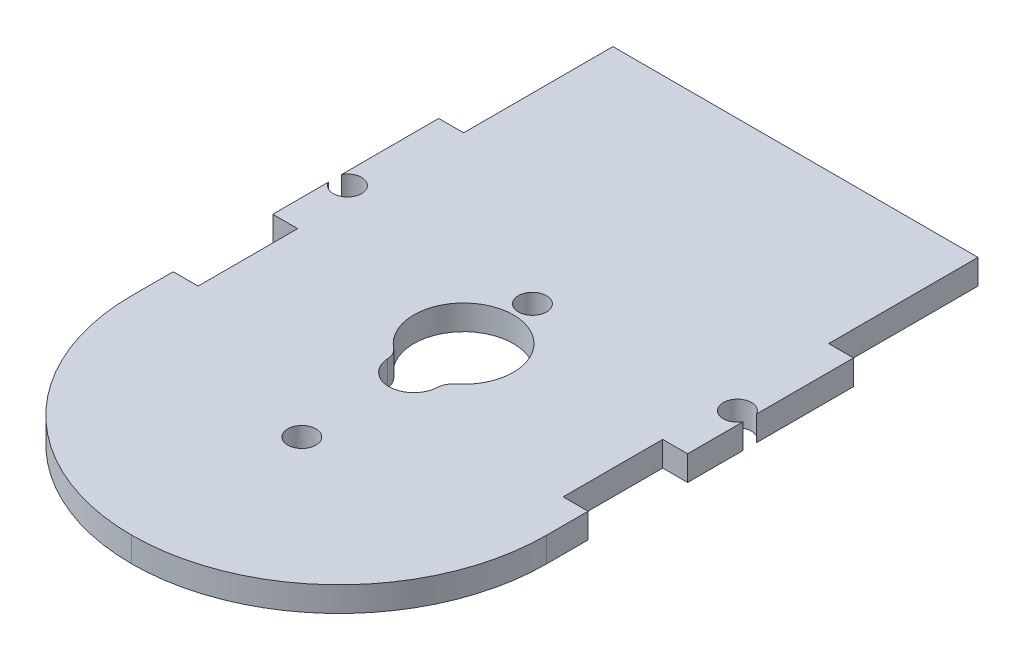
SolidWorks part; units mm, degrees
ref_plane "Front Plane" through (0, 0, 0) normal (0, 0, 1) x (1, 0, 0)
ref_plane "Top Plane" through (0, 0, 0) normal (0, 1, 0) x (1, 0, 0)
ref_plane "Right Plane" through (0, 0, 0) normal (1, 0, 0) x (0, 0, -1)
sketch "Sketch2" plane through (0, 0, 0) normal (0, 1, 0) x (1, 0, 0)
  line L1 (0, 0) -> (50, 0)
  line L2 (0, 0) -> (0, 80)
  line L3 (0, 80) -> (50, 80)
  line L4 (50, 0) -> (50, 80)
  dimension "D1" = 80
  dimension "D2" = 50
extrude "Boss-Extrude1" add sketch "Sketch2" along normal blind 3
hole_wizard "M4 Clearance Hole1" positions "Sketch3" profile "Sketch4" hole size "M4" standard "ANSI Metric"
sketch "Sketch3" plane through (0, 3, 0) normal (0, 1, 0) x (1, 0, 0)
  line L1 (50, 0) -> (50, 80) construction
  line L2 (50, 80) -> (0, 80) construction
  point P2 (25, 40)
  dimension "D1" = 40
  dimension "D4" = 25
sketch "Sketch4" plane through (25, 3, -40) normal (1, 0, 0) x (0, 0, 1)
  line L0 (0, 0) -> (0, 4.3519)
  line L1 (0, 4.3519) -> (2.25, 3)
  line L2 (2.25, 3) -> (2.25, 0)
  line L5 (2.25, 0) -> (0, 0)
  line L10 (0, 4.3519) -> (-2.25, 3) construction
  line L11 (0, -6.35) -> (0, 107.95) construction
  dimension "Hole Dia." = 4.5
  dimension "Hole Depth" = 3
  dimension "Drill Angle" = 118
sketch "Sketch5" plane through (0, 3, 0) normal (0, 1, 0) x (1, 0, 0)
  line L0 (50, 0) -> (50, 80) construction
  circle A0 centre (25, 40) radius 6
  circle A2 centre (25, 40) radius 2.25 construction
  dimension "D3" = 12
  dimension "D1" = 25
  dimension "D2" = 0
extrude "Cut-Extrude1" cut sketch "Sketch5" against normal blind 3
sketch "Sketch6" plane through (0, 3, 0) normal (0, 1, 0) x (1, 0, 0)
  circle A0 centre (25, 34) radius 3
  circle A2 centre (25, 40) radius 6 construction
extrude "Cut-Extrude2" cut sketch "Sketch6" against normal blind 3
fillet "Fillet1" radius 2 2 edges at (27.9047, 1.5, -34.75) (22.0953, 1.5, -34.75)
fillet "Fillet2" radius 25 2 edges at (0, 1.5, 0) (50, 1.5, 0)
sketch "Sketch7" plane through (0, 3, 0) normal (0, 1, 0) x (1, 0, 0)
  line L11 (50, 25) -> (50, 80) construction
  line L16 (50, 80) -> (47, 80)
  line L17 (50, 80) -> (50, 62)
  line L18 (50, 62) -> (47, 62)
  line L19 (47, 80) -> (47, 62)
  line L20 (0, 80) -> (3, 80)
  line L21 (0, 80) -> (0, 62)
  line L22 (0, 62) -> (3, 62)
  line L23 (3, 80) -> (3, 62)
  line L24 (50, 42) -> (47, 42)
  line L25 (50, 42) -> (50, 30)
  line L26 (50, 30) -> (47, 30)
  line L27 (47, 42) -> (47, 30)
  line L28 (0, 80) -> (0, 25) construction
  line L29 (0, 42) -> (3, 42)
  line L30 (0, 42) -> (0, 30)
  line L31 (0, 30) -> (3, 30)
  line L32 (3, 42) -> (3, 30)
  dimension "D1" = 3
  dimension "D2" = 18
  dimension "D3" = 18
  dimension "D4" = 3
  dimension "D5" = 12
  dimension "D6" = 12
  dimension "D7" = 3
  dimension "D8" = 3
  dimension "D9" = 20
  dimension "D10" = 20
extrude "Cut-Extrude3" cut sketch "Sketch7" against normal blind 3
hole_wizard "M3 Clearance Hole1" positions "Sketch8" profile "Sketch9" hole size "M3" standard "ANSI Metric"
sketch "Sketch8" plane through (0, 3, 0) normal (0, 1, 0) x (1, 0, 0)
  arc A1 (28.7453, 35.3125) -> (21.2547, 35.3125) centre (25, 40) ccw construction
  point P0 (25, 48.3)
  point P3 (25, 20.5)
  dimension "D2" = 8.3
  dimension "D1" = 19.5
sketch "Sketch9" plane through (25, 3, -48.3) normal (1, 0, 0) x (0, 0, 1)
  line L0 (0, 0) -> (0, 4.0215)
  line L1 (0, 4.0215) -> (1.7, 3)
  line L2 (1.7, 3) -> (1.7, 0)
  line L5 (1.7, 0) -> (0, 0)
  line L10 (0, 4.0215) -> (-1.7, 3) construction
  line L11 (0, -6.35) -> (0, 107.95) construction
  dimension "Hole Dia." = 3.4
  dimension "Hole Depth" = 3
  dimension "Drill Angle" = 118
hole_wizard "M3 Clearance Hole2" positions "Sketch10" profile "Sketch11" hole size "M3" standard "ANSI Metric" end condition through all
sketch "Sketch10" plane through (0, 3, 0) normal (0, 1, 0) x (1, 0, 0)
  line L0 (0, 62) -> (0, 42) construction
  line L1 (50, 42) -> (50, 62) construction
  line L2 (3, 42) -> (0, 42) construction
  line L3 (50, 42) -> (47, 42) construction
  point P0 (1.5, 49.5)
  point P2 (48.5, 49.5)
  dimension "D1" = 1.5
  dimension "D2" = 1.5
  dimension "D3" = 7.5
  dimension "D4" = 7.5
sketch "Sketch11" plane through (1.5, 3, -49.5) normal (1, 0, 0) x (0, 0, 1)
  line L0 (0, 0) -> (0, 3)
  line L1 (0, 3) -> (1.7, 3)
  line L2 (1.7, 3) -> (1.7, 0)
  line L5 (1.7, 0) -> (0, 0)
  line L11 (0, -6.35) -> (0, 107.95) construction
  dimension "Thru Hole Dia." = 3.4
  dimension "Thru Hole Depth" = 3
equation "\"Servo_Angle\"=45"
equation "\"Big_Teeth\"= 24"
equation "\"Small_Teeth\"= 12"
equation "\"Kerf\"= 0.18mm"
equation "\"D9@Sketch7\"=50-18-12"
